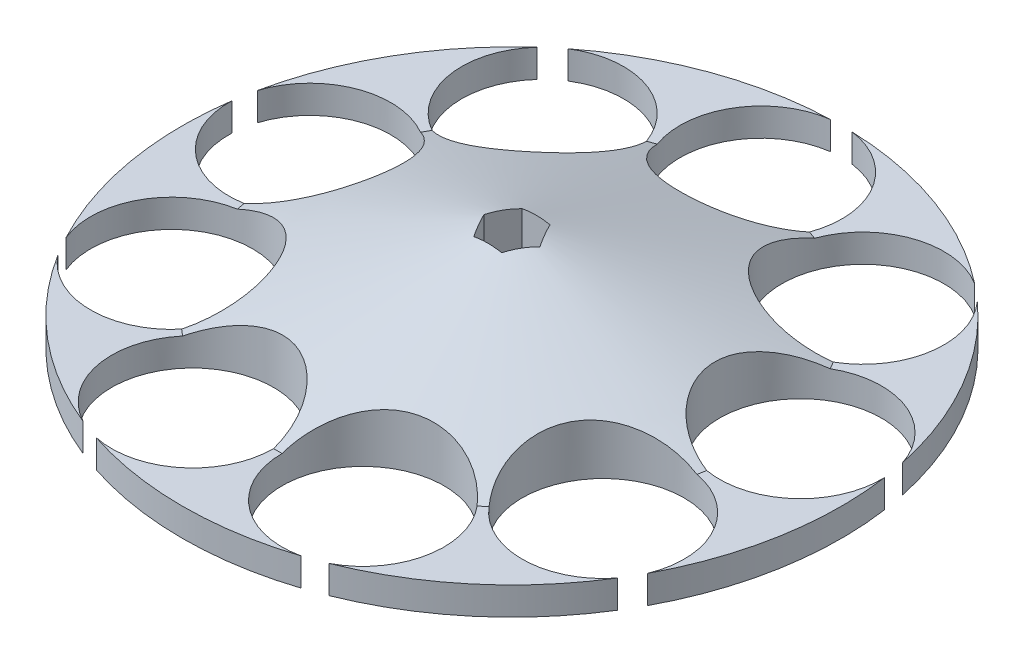
SolidWorks part; units mm, degrees
ref_plane "Front Plane" through (0, 0, 0) normal (0, 0, 1) x (1, 0, 0)
ref_plane "Top Plane" through (0, 0, 0) normal (0, 1, 0) x (1, 0, 0)
ref_plane "Right Plane" through (0, 0, 0) normal (1, 0, 0) x (0, 0, -1)
sketch "Sketch1" plane through (0, 0, 0) normal (0, 1, 0) x (1, 0, 0)
  line L0 (1.9842, -1.524) -> (1.9842, 1.524)
  arc A0 (1.9842, 1.524) -> (1.9842, -1.524) centre (0, 0) ccw
  circle A1 centre (0, 0) radius 8.255
  dimension "D1" = 2.5019
  dimension "D3" = 16.51
  dimension "D2" = 3.048
extrude "Boss-Extrude1" add sketch "Sketch1" along normal blind 5.08
sketch "Sketch5" plane through (0, 5.08, 0) normal (0, 1, 0) x (1, 0, 0)
  circle A0 centre (0, 0) radius 74.93
  circle A1 centre (0, 56.642) radius 18.415
  circle A2 centre (36.4088, 43.3903) radius 18.415
  circle A3 centre (55.7815, 9.8358) radius 18.415
  circle A4 centre (49.0534, -28.321) radius 18.415
  circle A5 centre (19.3727, -53.2261) radius 18.415
  circle A6 centre (-19.3727, -53.2261) radius 18.415
  circle A7 centre (-49.0534, -28.321) radius 18.415
  circle A8 centre (-55.7815, 9.8358) radius 18.415
  circle A9 centre (-36.4088, 43.3903) radius 18.415
  point P24 (0, 0)
  circle M3 centre (0, 0) radius 8.255
  line M4 (1.9842, 1.524) -> (1.9842, -1.524)
  arc M5 (1.9842, -1.524) -> (1.9842, 1.524) centre (0, 0) cw
  dimension "D1" = 149.86
  dimension "D2" = 36.83
  dimension "D3" = 0.127
  dimension "D4" = 9
extrude "Boss-Extrude4" add sketch "Sketch5" along normal blind 6.35 separate body contours A9 A0 A8 A7 A6 A5 A4 A3 A2 A1 M3 | M3 M5 M4 region at (70.6326, 5.08, 17.6769) region at (-8.0215, 5.08, 0)
sketch "Sketch6" plane through (0, 0, 0) normal (1, 0, 0) x (0, 0, -1)
  line L0 (0, 11.43) -> (0, 30.48) construction
  line L1 (10.5592, 11.43) -> (-35.2942, 11.43) construction
  line L2 (0, 30.48) -> (-53.2261, 11.43)
  line L3 (-53.2261, 11.43) -> (0, 11.43)
  line L4 (-34.8111, 11.43) -> (-71.6411, 11.43) construction
  line L5 (0, 11.43) -> (0, 30.48)
  dimension "D1" = 19.05
revolve "Revolve1" add sketch "Sketch6" angle 360 about L0
extrude "Cut-Extrude1" cut sketch "Sketch5<3>" along normal blind 21.59 contours A0 A6 | A0 A7 | A0 A8 | A0 A9 | A0 A1 | A0 A2 | A0 A3 | A0 A4 | A0 A5 region at (55.7743, 5.08, -9.8345) region at (49.0471, 5.08, 28.3174) region at (36.4041, 5.08, -43.3847) region at (19.3702, 5.08, 53.2193) region at (0, 5.08, -56.6348) region at (-19.3702, 5.08, 53.2193) region at (-36.4041, 5.08, -43.3847) region at (-49.0471, 5.08, 28.3174) region at (-55.7743, 5.08, -9.8345)
sketch "Sketch5<3>" plane through (0, 5.08, 0) normal (0, 1, 0) x (1, 0, 0) same geometry as "Sketch5"
extrude "Cut-Extrude2" cut sketch "Sketch1<2>" along normal through all contours L0 A0 region at (-0.1269, 0, 0)
sketch "Sketch1<2>" plane through (0, 0, 0) normal (0, 1, 0) x (1, 0, 0) same geometry as "Sketch1"
sketch "Sketch7" plane through (0, 0, 0) normal (0, 0, 1) x (1, 0, 0)
  line L1 (8.255, 0) -> (-8.255, 0)
  line L2 (8.255, 0) -> (8.255, 5.08)
  line L3 (8.255, 5.08) -> (-8.255, 5.08)
  line L4 (-8.255, 0) -> (-8.255, 5.08)
extrude "Cut-Extrude3" cut sketch "Sketch7" against normal mid plane 35.56
sketch "Sketch8" plane through (0, 5.08, 0) normal (0, -1, 0) x (1, 0, 0)
  line L1 (-3.175, -5.4993) -> (3.175, -5.4993)
  line L2 (3.175, -5.4993) -> (6.35, 0)
  line L3 (6.35, 0) -> (3.175, 5.4993)
  line L4 (3.175, 5.4993) -> (-3.175, 5.4993)
  line L5 (-3.175, 5.4993) -> (-6.35, 0)
  line L6 (-6.35, 0) -> (-3.175, -5.4993)
  circle A0 centre (0, 0) radius 5.4993 construction
  dimension "D1" = 12.7
extrude "Cut-Extrude4" cut sketch "Sketch8" against normal mid plane 53.34
